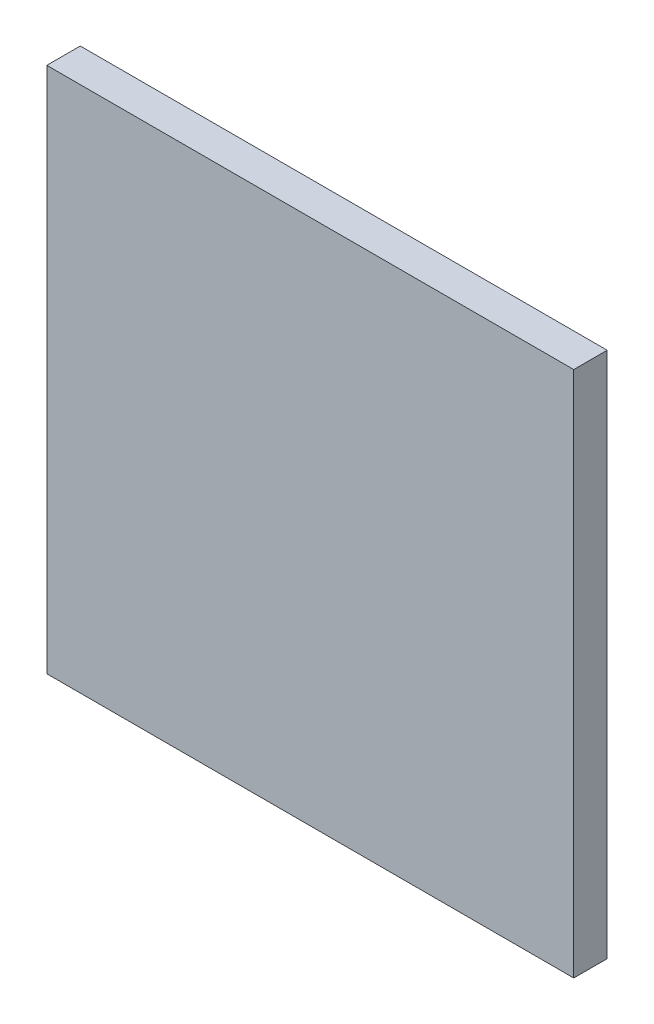
SolidWorks part; units mm, degrees
ref_plane "Front Plane" through (0, 0, 0) normal (0, 0, 1) x (1, 0, 0)
ref_plane "Top Plane" through (0, 0, 0) normal (0, 1, 0) x (1, 0, 0)
ref_plane "Right Plane" through (0, 0, 0) normal (1, 0, 0) x (0, 0, -1)
sketch "Sketch1" plane through (0, 0, 0) normal (0, 0, 1) x (1, 0, 0)
  line L1 (-3.15, -3.15) -> (3.15, -3.15)
  line L2 (-3.15, -3.15) -> (-3.15, 3.15)
  line L3 (-3.15, 3.15) -> (3.15, 3.15)
  line L4 (3.15, -3.15) -> (3.15, 3.15)
  line L5 (-3.15, -3.15) -> (3.15, 3.15) construction
  line L6 (-3.15, 3.15) -> (3.15, -3.15) construction
  point P0 (0, 0)
  dimension "D1" = 6.3
  dimension "D2" = 6.3
extrude "chip" add sketch "Sketch1" along normal blind 0.4
equation "\"pcb_length\"= 40 ' length of the chip in the direction of the feadline"
equation "\"pcb_side\"= 40    ' length of the chip in the other direction"
equation "\"pcb_width\"= 1"
equation "\"wall_width\"= 1  ' minimal width from the box walls"
equation "\"route_width\"= 1 ' The width of the trace on the lid for not touching the signal roates."
equation "\"route_clearence\"= 0.4 ' The clearence depth of the trace on the lid for not touching the signal roates."
equation "\"route_chip_clearence\"= 1"
equation "\"port_count\"= 2"
equation "\"port_space\"= 1.5"
equation "\"port_length\"= 5.1"
equation "\"port_width\"= 5.1"
equation "\"chip_length\"= 6.3 ' length of the chip in the direction of the feadline"
equation "\"chip_side\"= 6.3 ' length of the chip in the other direction"
equation "\"chip_width\"= 0.4 ' width of the chip"
equation "\"pedestal_depth\"= 10 ' depth of the pedestal under the chip"
equation "\"chip_leg\"= 0.8  ' size of the legs the chip lay on in case there is pedestal"
equation "\"wing_length\"= 10 ' Mounting wing size"
equation "\"wing_width\"= 1 ' mounting wing width"
equation "\"bonding_clearence\"= 1"
equation "\"box_height\"= \"wall_width\" + \"pedestal_depth\" + \"pcb_width\""
equation "\"box_length\"= \"pcb_length\" + 2 * \"wall_width\""
equation "\"box_side\"= \"pcb_side\" + 2 * \"wall_width\""
equation "\"D1@Sketch1\"=\"chip_length\""
equation "\"D2@Sketch1\"=\"chip_side\""
equation "\"D1@chip\"=\"chip_width\""
